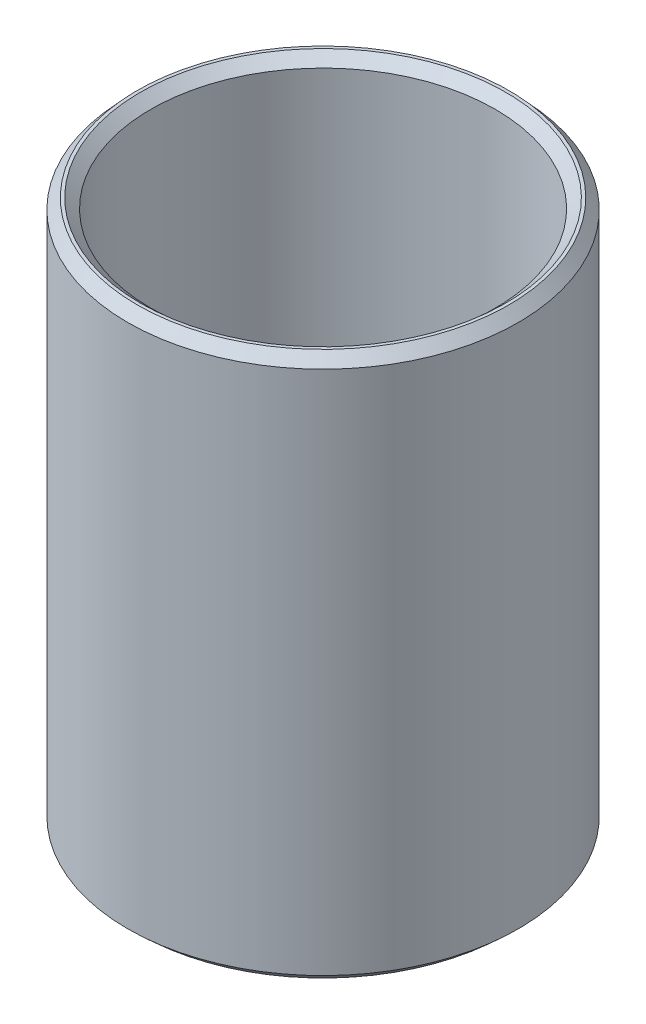
SolidWorks part; units mm, degrees
ref_plane "Front Plane" through (0, 0, 0) normal (0, 0, 1) x (1, 0, 0)
ref_plane "Top Plane" through (0, 0, 0) normal (0, 1, 0) x (1, 0, 0)
ref_plane "Right Plane" through (0, 0, 0) normal (1, 0, 0) x (0, 0, -1)
sketch "Sketch1" plane through (0, 0, 0) normal (0, 1, 0) x (1, 0, 0)
  circle A0 centre (0, 0) radius 57.5
  dimension "SLEEVE_OD" = 115
extrude "Boss-Extrude1" add sketch "Sketch1" along normal blind 160.4807
sketch "Sketch2" plane through (0, 0, 0) normal (0, 1, 0) x (1, 0, 0)
  circle A0 centre (0, 0) radius 50.705
  dimension "BORE_D" = 101.4101
extrude "Cut-Extrude1" cut sketch "Sketch2" along normal through all
chamfer "Chamfer1" distance 3.0763 angle 42.361 4 edges at (0, 160.4807, 50.705) (0, 0, 50.705) (0, 0, 57.5) (0, 160.4807, 57.5) first distance on face at (0, 160.4807, 50.705) first distance on face at (0, 0, 50.705) first distance on face at (0, 160.4807, 57.5)
